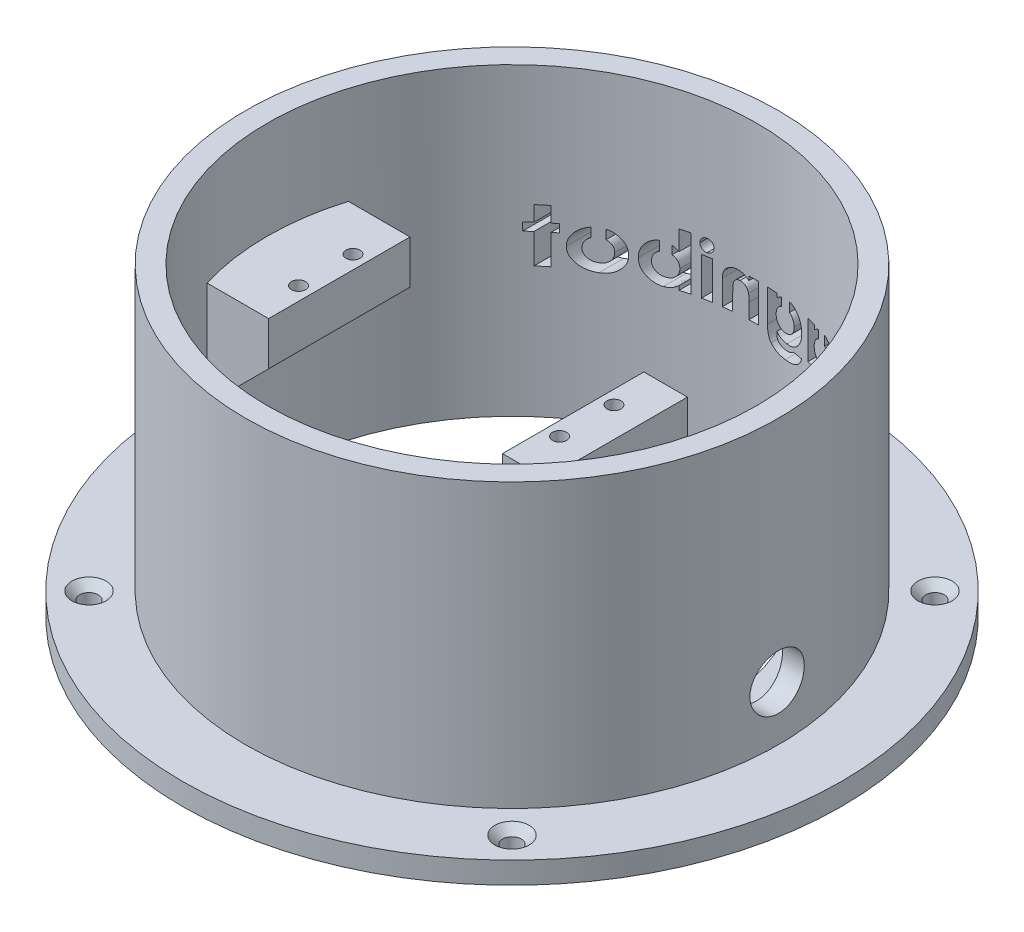
SolidWorks part; units mm, degrees
ref_plane "Front Plane" through (0, 0, 0) normal (0, 0, 1) x (1, 0, 0)
ref_plane "Top Plane" through (0, 0, 0) normal (0, 1, 0) x (1, 0, 0)
ref_plane "Right Plane" through (0, 0, 0) normal (1, 0, 0) x (0, 0, -1)
sketch "Sketch1" plane through (0, 0, 0) normal (0, 1, 0) x (1, 0, 0)
  circle A0 centre (0, 0) radius 60.625
  circle A1 centre (0, 0) radius 45
  dimension "D1" = 121.25
  dimension "D2" = 90
extrude "Boss-Extrude1" add sketch "Sketch1" along normal blind 4
sketch "Sketch2" plane through (0, 4, 0) normal (0, 1, 0) x (1, 0, 0)
  circle A0 centre (0, 0) radius 45 construction
  circle A1 centre (0, 0) radius 45
  circle A2 centre (0, 0) radius 49
  dimension "D1" = 4
extrude "Boss-Extrude2" add sketch "Sketch2" along normal blind 52
ref_plane "Plane1" through (0, 36, 0) normal (0, 1, 0) x (1, 0, 0)
sketch "Sketch4" plane through (0, 0, 0) normal (0, 0, 1) x (1, 0, 0)
  line L0 (-60.625, 0) -> (60.625, 0) construction
  line L1 (11.25, 38) -> (19.25, 38)
  line L2 (11.25, 38) -> (11.25, 0)
  line L3 (11.25, 0) -> (19.25, 0)
  line L4 (19.25, 38) -> (19.25, 0)
  line L5 (49, 56) -> (-49, 56) construction
  line L6 (-45, 56) -> (-45, 4)
  line L7 (-31.75, 38) -> (-46.75, 38)
  line L8 (-31.75, 38) -> (-31.75, 30)
  line L9 (-31.75, 30) -> (-46.75, 30)
  line L10 (-46.75, 38) -> (-46.75, 30)
  line L11 (60.625, 4) -> (-60.625, 4) construction
  line L12 (-31.75, 30) -> (-45, 16.75)
  dimension "D1" = 11.25
  dimension "D2" = 8
  dimension "D3" = 18
  dimension "D4" = 43
  dimension "D5" = 15
  dimension "D6" = 8
  dimension "D7" = 45
  dimension "D8" = 18
extrude "Boss-Extrude4" add sketch "Sketch4" along normal mid plane 26 contours L9 L8 L7 L6 | L12 L9 L6 | L1 L4 L3 L2 region at (-38.375, 34, 0) region at (-40.5833, 25.5833, 0)
sketch "Sketch5" plane through (0, 0, 0) normal (0, -1, 0) x (1, 0, 0)
  line L0 (11.25, 13) -> (29.0674, 34.3524)
  line L1 (11.25, -13) -> (29.0674, -34.3524)
  line L2 (11.25, 13) -> (11.25, -13)
  circle A0 centre (0, 0) radius 45 construction
  arc A1 (29.0674, -34.3524) -> (29.0674, 34.3524) centre (0, 0) ccw
extrude "Boss-Extrude5" add sketch "Sketch5" against normal up to surface (4 mm away) contours L0 A1 L1 L2 up to face at (0, 4, 60.625)
sketch "Sketch7" plane through (0, 38, 0) normal (0, 1, 0) x (1, 0, 0)
  line L0 (-31.75, -13) -> (-31.75, 13) construction
  circle A0 centre (-34.25, 5) radius 1.3
  circle A1 centre (-34.25, -5) radius 1.3
  circle A2 centre (13.75, 5) radius 1.3
  circle A3 centre (13.75, -5) radius 1.3
  dimension "D1" = 2.6
  dimension "D2" = 2.6
  dimension "D3" = 10
  dimension "D4" = 5
  dimension "D5" = 2.5
  dimension "D7" = 48
  dimension "D6" = 2
extrude "Cut-Extrude4" cut sketch "Sketch7" against normal blind 7.2
sketch "Sketch9" plane through (11.25, 0, 0) normal (-1, 0, 0) x (0, 0, 1)
  line L0 (13, 0) -> (-13, 0) construction
  line L1 (-5, 29) -> (5, 29)
  line L2 (-5, 29) -> (-5, 0)
  line L3 (-5, 0) -> (5, 0)
  line L4 (5, 29) -> (5, 0)
  line L5 (-5, 29) -> (5, 0) construction
  line L6 (-5, 0) -> (5, 29) construction
  line L7 (0, 0) -> (0, 29) construction
  line L8 (13, 38) -> (-13, 38) construction
  line L10 (5, 5) -> (-5, 5)
  point P0 (0, 14.5)
  dimension "D1" = 10
  dimension "D2" = 9
  dimension "D3" = 5
extrude "Cut-Extrude7" cut sketch "Sketch9" against normal up to surface (8 mm away) contours L10 L4 L1 L2 region at (11.25, 17, 0) up to face at (19.25, 21, 0)
ref_plane "Plane2" through (49, 0, 0) normal (1, 0, 0) x (0, 0, -1)
sketch "Sketch11" plane through (49, 0, 0) normal (1, 0, 0) x (0, 0, -1)
  circle A0 centre (0, 14) radius 5
  dimension "D1" = 10
  dimension "D2" = 14
extrude "Cut-Extrude8" cut sketch "Sketch11" against normal up to next
sketch "Sketch12" plane through (0, 4, 0) normal (0, 1, 0) x (1, 0, 0)
  line L5 (27.25, 19.6878) -> (27.25, -19.6878)
  line L6 (27.25, 19.6878) -> (27.25, -19.6878)
  line L9 (24.25, 16.0926) -> (24.25, -16.0926)
  line L10 (19.25, -13) -> (19.25, 13) construction
  line L18 (27.25, -19.6878) -> (29.4795, -22.3597)
  line L19 (29.4795, 22.3597) -> (27.25, 19.6878)
  line L21 (24.25, -16.0926) -> (29.4795, -22.3597)
  line L22 (29.4795, 22.3597) -> (24.25, 16.0926)
  arc A2 (29.4795, -22.3597) -> (29.4795, 22.3597) centre (0, 0) ccw
  arc A3 (29.4795, -22.3597) -> (29.4795, 22.3597) centre (0, 0) ccw
  dimension "D2" = 5
  dimension "D1" = 8
extrude "Cut-Extrude9" cut sketch "Sketch12" against normal through all contours L21 A3 L22 L6 | L6 L22 L9 L21 region at (31.3175, 4, 0) region at (25.8002, 4, 0)
sketch "Sketch14" plane through (0, 4, 0) normal (0, 1, 0) x (1, 0, 0)
  line L0 (0, 0) -> (-38.8909, 38.8909) construction
  line L1 (11.25, 13) -> (19.25, 13) construction
  circle A0 centre (-38.8909, 38.8909) radius 1.5
  circle A1 centre (38.8909, 38.8909) radius 1.5
  circle A2 centre (38.8909, -38.8909) radius 1.5
  circle A3 centre (-38.8909, -38.8909) radius 1.5
  point P15 (0, 0)
  dimension "D1" = 3
  dimension "D2" = 55
  dimension "D3" = 135
  dimension "D4" = 4
hole_wizard "CSK for M3 Countersunk Flat Head Screw1" positions "Sketch15" profile "Sketch17" countersink size "M3" standard "DIN" end condition up to next
sketch "Sketch15" plane through (0, 4, 0) normal (0, 1, 0) x (1, 0, 0)
  point P0 (-38.8909, 38.8909)
  point P3 (-38.8909, -38.8909)
  point P6 (38.8909, -38.8909)
  point P9 (38.8909, 38.8909)
sketch "Sketch17" plane through (-38.8909, 4, -38.8909) normal (1, 0, 0) x (0, 0, 1)
  line L0 (0, 0) -> (0, 4)
  line L1 (0, 4) -> (1.7, 4)
  line L2 (1.7, 4) -> (1.7, 1.45)
  line L3 (1.7, 1.45) -> (3.15, 0)
  line L5 (3.15, 0) -> (0, 0)
  line L6 (-1.7, 1.45) -> (-3.15, 0) construction
  line L11 (0, -6.35) -> (0, 107.95) construction
  dimension "Thru Hole Dia." = 3.4
  dimension "Thru Hole Depth" = 4
  dimension "Near C'Sink Dia." = 6.3
  dimension "Near C'Sink Angle" = 90
sketch "Sketch18" plane through (0, 0, -13) normal (0, 0, -1) x (-1, 0, 0)
  line L1 (28.0255, 33.7692) -> (29.7351, 33.7692)
  line L2 (29.7351, 33.7692) -> (29.7351, 30.9606)
  line L3 (29.7351, 30.9606) -> (30.8341, 30.9606)
  line L4 (30.8341, 30.9606) -> (30.8341, 29.4952)
  line L5 (30.8341, 29.4952) -> (29.7351, 29.4952)
  line L6 (29.7351, 29.4952) -> (29.7351, 24)
  line L7 (29.7351, 24) -> (28.0255, 24)
  line L8 (28.0255, 24) -> (28.0255, 29.4952)
  line L9 (28.0255, 29.4952) -> (27.1707, 29.4952)
  line L10 (27.1707, 29.4952) -> (27.1707, 30.9606)
  line L11 (27.1707, 30.9606) -> (28.0255, 30.9606)
  line L12 (28.0255, 30.9606) -> (28.0255, 33.7692)
  line L13 (12.5168, 33.7692) -> (12.5168, 30.1497)
  line L14 (12.5168, 24.7594) -> (12.5168, 24)
  line L15 (12.5168, 24) -> (10.8072, 24)
  line L16 (10.8072, 24) -> (10.8072, 33.7692)
  line L17 (10.8072, 33.7692) -> (12.5168, 33.7692)
  line L18 (7.5101, 30.9606) -> (9.2197, 30.9606)
  line L19 (9.2197, 30.9606) -> (9.2197, 24)
  line L20 (9.2197, 24) -> (7.5101, 24)
  line L21 (7.5101, 24) -> (7.5101, 30.9606)
  line L22 (-0.3053, 30.9606) -> (1.4043, 30.9606)
  line L23 (1.4043, 30.9606) -> (1.4043, 30.2241)
  line L24 (5.9226, 28.5641) -> (5.9226, 24)
  line L25 (5.9226, 24) -> (4.213, 24)
  line L26 (4.213, 24) -> (4.213, 27.0224)
  line L27 (1.4043, 26.7705) -> (1.4043, 24)
  line L28 (1.4043, 24) -> (-0.3053, 24)
  line L29 (-0.3053, 24) -> (-0.3053, 30.9606)
  line L30 (-3.8466, 30.9606) -> (-2.0149, 30.9606)
  line L31 (-2.0149, 30.9606) -> (-2.0149, 25.0227)
  line L32 (-9.2273, 23.5115) -> (-7.3269, 23.5115)
  line L33 (-3.8466, 30.1859) -> (-3.8466, 30.9606)
  line L34 (-12.3947, 30.9606) -> (-10.6851, 30.9606)
  line L35 (-10.6851, 30.9606) -> (-10.6851, 24)
  line L36 (-10.6851, 24) -> (-12.3947, 24)
  line L37 (-12.3947, 24) -> (-12.3947, 24.7594)
  line L38 (-12.3947, 30.1764) -> (-12.3947, 30.9606)
  line L39 (-30.1014, 30.9606) -> (-28.3918, 30.9606)
  line L40 (-28.3918, 30.9606) -> (-28.3918, 30.1287)
  line L41 (-19.3553, 28.0489) -> (-19.3553, 24)
  line L42 (-19.3553, 24) -> (-21.0649, 24)
  line L43 (-21.0649, 24) -> (-21.0649, 27.4956)
  line L44 (-23.8736, 27.1082) -> (-23.8736, 24)
  line L45 (-23.8736, 24) -> (-25.5832, 24)
  line L46 (-25.5832, 24) -> (-25.5832, 27.3372)
  line L47 (-28.3918, 27.0643) -> (-28.3918, 24)
  line L48 (-28.3918, 24) -> (-30.1014, 24)
  line L49 (-30.1014, 24) -> (-30.1014, 30.9606)
  line L51 (-15.1048, 31.4629) -> (-13.3948, 31.4629)
  line L52 (-15.1048, 31.4629) -> (-15.1048, 28.9712)
  line L53 (-15.1048, 28.9712) -> (-13.3948, 28.9712)
  line L54 (-13.3948, 31.4629) -> (-13.3948, 28.9712)
  line L55 (-6.4773, 31.5143) -> (-4.7673, 31.5143)
  line L56 (-6.4773, 31.5143) -> (-6.4773, 29.0876)
  line L57 (-6.4773, 29.0876) -> (-4.7673, 29.0876)
  line L58 (-4.7673, 31.5143) -> (-4.7673, 29.0876)
  line L59 (13.5081, 31.593) -> (15.2181, 31.593)
  line L60 (13.5081, 31.593) -> (13.5081, 28.9616)
  line L61 (13.5081, 28.9616) -> (15.2181, 28.9616)
  line L62 (15.2181, 31.593) -> (15.2181, 28.9616)
  line L63 (21.9818, 31.4887) -> (23.6918, 31.4887)
  line L64 (21.9818, 31.4887) -> (21.9818, 28.7761)
  line L65 (21.9818, 28.7761) -> (23.6918, 28.7761)
  line L66 (23.6918, 31.4887) -> (23.6918, 28.7761)
  spline S0 degree 3 poles (22.7936, 31.0827) (22.9536, 31.0827) (23.1931, 31.0681) (23.5072, 31.016) (23.7386, 30.9659) (23.965, 30.8957) (24.1877, 30.8115) (24.4086, 30.7149) (24.6222, 30.5998) (24.83, 30.4751) (25.0271, 30.3374) (25.2118, 30.188) (25.3874, 30.0303) (25.5458, 29.8573) (25.6972, 29.6776) (25.8334, 29.4845) (25.9594, 29.2828) (26.0716, 29.0738) (26.169, 28.8587) (26.2536, 28.6407) (26.3198, 28.417) (26.3746, 28.1906) (26.4213, 27.88) (26.4389, 27.6443) (26.438, 27.486) knots 0 0 0 0 0.084364 0.126142 0.167706 0.209066 0.250973 0.293148 0.336041 0.378761 0.420893 0.462622 0.503914 0.545188 0.586138 0.627722 0.669585 0.711432 0.752691 0.793971 0.834592 0.875577 0.91664 1 1 1 1
  spline S1 degree 3 poles (26.438, 27.486) (26.4378, 27.3266) (26.4236, 27.0883) (26.3713, 26.7763) (26.321, 26.5461) (26.2511, 26.3218) (26.1694, 26.1) (26.0691, 25.8836) (25.9582, 25.6704) (25.8314, 25.4666) (25.6953, 25.2716) (25.5446, 25.0905) (25.3874, 24.9177) (25.2164, 24.759) (25.0341, 24.6119) (24.8423, 24.4746) (24.6396, 24.3502) (24.4285, 24.2409) (24.2126, 24.1424) (23.9906, 24.0604) (23.763, 23.9934) (23.5297, 23.9417) (23.2093, 23.8941) (22.9652, 23.8771) (22.8012, 23.8779) knots 0 0 0 0 0.083839 0.125192 0.166335 0.207602 0.24867 0.290582 0.332926 0.374978 0.416741 0.457857 0.498809 0.539516 0.58042 0.62191 0.663502 0.705394 0.746864 0.788245 0.829736 0.871532 0.913825 1 1 1 1
  spline S2 degree 3 poles (22.8012, 23.8779) (22.5631, 23.8803) (22.2083, 23.9072) (21.7532, 24.019) (21.429, 24.1339) (21.1177, 24.2814) (20.822, 24.4638) (20.5389, 24.6777) (20.2733, 24.9212) (20.03, 25.1884) (19.8174, 25.4736) (19.6369, 25.7726) (19.4887, 26.0857) (19.3743, 26.4132) (19.2623, 26.874) (19.2355, 27.2332) (19.2332, 27.4746) knots 0 0 0 0 0.126884 0.188201 0.248894 0.309599 0.371125 0.433466 0.498143 0.562593 0.625474 0.687114 0.748125 0.809457 0.871431 1 1 1 1
  spline S3 degree 3 poles (19.2332, 27.4746) (19.2336, 27.7324) (19.2684, 28.1141) (19.3922, 28.6033) (19.5227, 28.9481) (19.6897, 29.2762) (19.9647, 29.6971) (20.2255, 29.9763) (20.4143, 30.1497) knots 0 0 0 0 0.256474 0.379237 0.500978 0.622367 0.744855 1 1 1 1
  spline S4 degree 3 poles (20.4143, 30.1497) (20.5802, 30.3024) (20.8481, 30.5037) (21.2311, 30.7219) (21.5244, 30.8552) (21.8286, 30.9555) (22.2495, 31.0542) (22.575, 31.0818) (22.7936, 31.0827) knots 0 0 0 0 0.258464 0.38258 0.504991 0.627227 0.749297 1 1 1 1
  spline S5 degree 3 poles (22.8318, 29.4952) (22.7019, 29.4917) (22.5077, 29.4823) (22.2621, 29.4178) (22.0874, 29.3572) (21.9227, 29.2762) (21.7633, 29.1814) (21.6176, 29.0627) (21.4785, 28.9326) (21.3522, 28.7881) (21.2446, 28.6306) (21.1485, 28.4663) (21.0755, 28.289) (21.0153, 28.1036) (20.9595, 27.8373) (20.9404, 27.6306) (20.9428, 27.4898) knots 0 0 0 0 0.126803 0.187423 0.246518 0.306285 0.365703 0.426477 0.488622 0.550895 0.612679 0.673914 0.735734 0.798735 0.86329 1 1 1 1
  spline S6 degree 3 poles (20.9428, 27.4898) (20.9422, 27.3456) (20.9565, 27.1333) (21.0136, 26.8609) (21.0729, 26.672) (21.1476, 26.4928) (21.2392, 26.3242) (21.3487, 26.1674) (21.4728, 26.0226) (21.6088, 25.891) (21.7577, 25.7782) (21.9134, 25.6801) (22.0795, 25.6014) (22.2535, 25.5406) (22.5012, 25.4797) (22.6954, 25.468) (22.826, 25.4654) knots 0 0 0 0 0.139456 0.204809 0.268587 0.330587 0.392213 0.45361 0.515092 0.576402 0.636039 0.695407 0.753981 0.813285 0.873377 1 1 1 1
  spline S7 degree 3 poles (22.826, 25.4654) (22.9571, 25.4658) (23.1512, 25.4829) (23.3999, 25.5421) (23.5754, 25.6033) (23.7416, 25.6838) (23.899, 25.7823) (24.0491, 25.8968) (24.1868, 26.0308) (24.3144, 26.1761) (24.4262, 26.3337) (24.5196, 26.5022) (24.5963, 26.6806) (24.6557, 26.8685) (24.7119, 27.1379) (24.7308, 27.3472) (24.7284, 27.4898) knots 0 0 0 0 0.126397 0.186939 0.246099 0.305348 0.364572 0.424924 0.486952 0.54955 0.611149 0.672922 0.73501 0.798049 0.862643 1 1 1 1
  spline S8 degree 3 poles (24.7284, 27.4898) (24.7289, 27.6322) (24.7144, 27.8419) (24.6579, 28.1106) (24.5978, 28.2968) (24.5236, 28.4736) (24.4319, 28.6402) (24.3219, 28.7958) (24.1971, 28.9395) (24.0592, 29.0692) (23.9128, 29.1849) (23.7547, 29.2805) (23.5879, 29.3593) (23.4118, 29.42) (23.161, 29.4811) (22.9643, 29.4923) (22.8318, 29.4952) knots 0 0 0 0 0.13784 0.202698 0.265406 0.326938 0.388125 0.449117 0.511101 0.572086 0.632197 0.691339 0.750564 0.810546 0.871335 1 1 1 1
  spline S9 degree 3 poles (12.5168, 30.1497) (12.6689, 30.2999) (12.913, 30.5045) (13.2701, 30.721) (13.5425, 30.8554) (13.8263, 30.9547) (14.2179, 31.0586) (14.5242, 31.079) (14.7283, 31.0827) knots 0 0 0 0 0.260396 0.385476 0.507708 0.62942 0.750914 1 1 1 1
  spline S10 degree 3 poles (14.7283, 31.0827) (14.9489, 31.0835) (15.2774, 31.0537) (15.6975, 30.9454) (15.9965, 30.8341) (16.2816, 30.6893) (16.5559, 30.5161) (16.8147, 30.3071) (17.0582, 30.0704) (17.2834, 29.811) (17.4794, 29.5289) (17.6425, 29.228) (17.7809, 28.9116) (17.8817, 28.5747) (17.9877, 28.0953) (18.0097, 27.72) (18.012, 27.4669) knots 0 0 0 0 0.12138 0.180256 0.238142 0.296489 0.355776 0.416247 0.479076 0.54232 0.604902 0.667516 0.730346 0.794405 0.860608 1 1 1 1
  spline S11 degree 3 poles (18.012, 27.4669) (18.0112, 27.2212) (17.9853, 26.8569) (17.8789, 26.39) (17.7693, 26.061) (17.6298, 25.7471) (17.4595, 25.4483) (17.2574, 25.1658) (17.0264, 24.9033) (16.774, 24.6656) (16.511, 24.4523) (16.2322, 24.2776) (15.9446, 24.1299) (15.6435, 24.0172) (15.2231, 23.91) (14.8966, 23.875) (14.6767, 23.8779) knots 0 0 0 0 0.135343 0.199959 0.263049 0.325881 0.388744 0.451973 0.516706 0.580831 0.6426 0.702706 0.761562 0.820266 0.879182 1 1 1 1
  spline S12 degree 3 poles (14.6767, 23.8779) (14.4813, 23.879) (14.1903, 23.9014) (13.8164, 23.9898) (13.5471, 24.0796) (13.2849, 24.2024) (12.9279, 24.4129) (12.6786, 24.6134) (12.5168, 24.7594) knots 0 0 0 0 0.245253 0.364043 0.481077 0.600625 0.726476 1 1 1 1
  spline S13 degree 3 poles (14.3581, 29.4952) (14.2224, 29.4925) (14.0206, 29.4811) (13.7637, 29.4198) (13.5821, 29.3613) (13.4104, 29.2824) (13.2472, 29.1868) (13.0939, 29.0727) (12.9496, 28.9448) (12.82, 28.8008) (12.7049, 28.647) (12.6094, 28.4813) (12.5298, 28.3059) (12.4697, 28.1188) (12.409, 27.8506) (12.3972, 27.6408) (12.3947, 27.4994) knots 0 0 0 0 0.129944 0.191681 0.251804 0.311878 0.37178 0.43216 0.494106 0.5556 0.61683 0.677256 0.737884 0.800505 0.864611 1 1 1 1
  spline S14 degree 3 poles (12.3947, 27.4994) (12.3973, 27.3547) (12.409, 27.1406) (12.4693, 26.8672) (12.5306, 26.6767) (12.6089, 26.497) (12.7043, 26.3272) (12.8207, 26.1712) (12.9489, 26.0235) (13.094, 25.8938) (13.2466, 25.7775) (13.4104, 25.6817) (13.5829, 25.6041) (13.7629, 25.5396) (14.0209, 25.4803) (14.2222, 25.4676) (14.3581, 25.4654) knots 0 0 0 0 0.137034 0.201676 0.264245 0.325918 0.386785 0.447889 0.509667 0.571399 0.631536 0.690841 0.750317 0.810229 0.871351 1 1 1 1
  spline S15 degree 3 poles (14.3581, 25.4654) (14.4904, 25.4663) (14.6858, 25.4825) (14.9372, 25.5423) (15.1143, 25.6051) (15.2837, 25.6869) (15.4466, 25.7826) (15.5976, 25.9021) (15.7426, 26.0336) (15.8723, 26.1818) (15.9886, 26.3392) (16.0864, 26.5074) (16.164, 26.6867) (16.2281, 26.8738) (16.2876, 27.1426) (16.2999, 27.3521) (16.3024, 27.4936) knots 0 0 0 0 0.1264 0.186368 0.246314 0.305548 0.365765 0.426397 0.489164 0.552425 0.614149 0.675935 0.737677 0.800494 0.864605 1 1 1 1
  spline S16 degree 3 poles (16.3024, 27.4936) (16.2994, 27.6337) (16.2886, 27.8419) (16.2268, 28.1069) (16.1694, 28.2934) (16.0892, 28.4684) (15.9943, 28.634) (15.8827, 28.7908) (15.7531, 28.9344) (15.6111, 29.0651) (15.4595, 29.1807) (15.2988, 29.2792) (15.127, 29.3568) (14.9481, 29.4206) (14.6922, 29.4804) (14.4927, 29.4929) (14.3581, 29.4952) knots 0 0 0 0 0.134802 0.198611 0.260756 0.321667 0.382903 0.4437 0.505935 0.568128 0.628667 0.688638 0.748437 0.809234 0.870665 1 1 1 1
  spline S17 degree 3 poles (8.3611, 33.8913) (8.5057, 33.8937) (8.7226, 33.8489) (8.977, 33.7027) (9.1452, 33.5539) (9.285, 33.3759) (9.4295, 33.1075) (9.4611, 32.8768) (9.4639, 32.7255) knots 0 0 0 0 0.242963 0.363855 0.490606 0.61874 0.7433 1 1 1 1
  spline S18 degree 3 poles (9.4639, 32.7255) (9.4628, 32.5754) (9.4267, 32.3489) (9.2879, 32.0806) (9.147, 31.9053) (8.9806, 31.7588) (8.732, 31.6103) (8.5162, 31.5712) (8.3744, 31.5712) knots 0 0 0 0 0.256469 0.381955 0.510704 0.637377 0.757775 1 1 1 1
  spline S19 degree 3 poles (8.3744, 31.5712) (8.2284, 31.5686) (8.0103, 31.614) (7.7524, 31.7591) (7.5849, 31.9109) (7.4436, 32.0902) (7.3049, 32.3653) (7.2655, 32.5959) (7.2659, 32.7503) knots 0 0 0 0 0.242759 0.363443 0.489711 0.617482 0.74228 1 1 1 1
  spline S20 degree 3 poles (7.2659, 32.7503) (7.2683, 32.8988) (7.3018, 33.124) (7.4428, 33.3874) (7.5816, 33.5622) (7.7483, 33.7082) (8.0025, 33.8499) (8.2174, 33.8925) (8.3611, 33.8913) knots 0 0 0 0 0.255027 0.378937 0.506523 0.634371 0.754976 1 1 1 1
  spline S21 degree 3 poles (1.4043, 30.2241) (1.5881, 30.3723) (1.8638, 30.5692) (2.2391, 30.781) (2.4966, 30.8962) (2.749, 30.9789) (3.0835, 31.0586) (3.3399, 31.0837) (3.5108, 31.0827) knots 0 0 0 0 0.304989 0.436681 0.556242 0.668759 0.779379 1 1 1 1
  spline S22 degree 3 poles (3.5108, 31.0827) (3.6804, 31.0808) (3.9334, 31.0645) (4.2568, 30.9851) (4.4874, 30.9076) (4.7072, 30.8051) (4.9922, 30.6415) (5.182, 30.4798) (5.3025, 30.3653) knots 0 0 0 0 0.257369 0.381171 0.503299 0.625248 0.747811 1 1 1 1
  spline S23 degree 3 poles (5.3025, 30.3653) (5.4059, 30.2627) (5.5432, 30.0886) (5.6853, 29.8262) (5.7737, 29.6095) (5.8389, 29.3729) (5.908, 29.0248) (5.9215, 28.7507) (5.9226, 28.5641) knots 0 0 0 0 0.22321 0.337546 0.456528 0.581244 0.713405 1 1 1 1
  spline S24 degree 3 poles (4.213, 27.0224) (4.2125, 27.2112) (4.2108, 27.4817) (4.1962, 27.8244) (4.1868, 28.0428) (4.1682, 28.2348) (4.1514, 28.4014) (4.1257, 28.5411) (4.0922, 28.6915) (4.0338, 28.8525) (3.943, 29.0221) (3.8279, 29.1662) (3.6932, 29.2858) (3.5389, 29.3803) (3.303, 29.4721) (3.1097, 29.4957) (2.9785, 29.4952) knots 0 0 0 0 0.179518 0.256937 0.32593 0.387213 0.440139 0.484952 0.522188 0.586422 0.647004 0.704202 0.760716 0.817414 0.875213 1 1 1 1
  spline S25 degree 3 poles (2.9785, 29.4952) (2.8055, 29.4934) (2.5449, 29.4553) (2.234, 29.3024) (2.0255, 29.1462) (1.8416, 28.9531) (1.6327, 28.637) (1.531, 28.3636) (1.4845, 28.171) knots 0 0 0 0 0.240658 0.35739 0.477137 0.600009 0.725225 1 1 1 1
  spline S26 degree 3 poles (1.4845, 28.171) (1.4665, 28.1021) (1.4533, 27.9851) (1.4322, 27.8146) (1.4255, 27.6513) (1.4141, 27.4645) (1.4081, 27.168) (1.4044, 26.934) (1.4043, 26.7705) knots 0 0 0 0 0.151476 0.251213 0.366854 0.500124 0.650932 1 1 1 1
  spline S27 degree 3 poles (-2.0149, 25.0227) (-2.0161, 24.7489) (-2.0329, 24.3502) (-2.1079, 23.8416) (-2.1856, 23.5018) (-2.2863, 23.192) (-2.4455, 22.8255) (-2.6034, 22.5793) (-2.7266, 22.4354) knots 0 0 0 0 0.300234 0.436257 0.562885 0.681681 0.792784 1 1 1 1
  spline S28 degree 3 poles (-2.7266, 22.4354) (-2.8834, 22.2492) (-3.1574, 22.0013) (-3.5792, 21.7441) (-3.9268, 21.5849) (-4.3051, 21.4638) (-4.8649, 21.3434) (-5.3059, 21.3128) (-5.6078, 21.3135) knots 0 0 0 0 0.228421 0.343997 0.462956 0.586703 0.716303 1 1 1 1
  spline S29 degree 3 poles (-5.6078, 21.3135) (-5.9233, 21.3133) (-6.3802, 21.3376) (-6.9551, 21.4475) (-7.33, 21.5582) (-7.6699, 21.7012) (-7.9812, 21.8726) (-8.2633, 22.0776) (-8.5206, 22.3079) (-8.7467, 22.5689) (-9.0083, 22.9588) (-9.1528, 23.2846) (-9.2273, 23.5115) knots 0 0 0 0 0.207411 0.299345 0.383942 0.46371 0.541137 0.616855 0.692287 0.767513 0.843065 1 1 1 1
  spline S30 degree 3 poles (-7.3269, 23.5115) (-7.2424, 23.411) (-7.0944, 23.2762) (-6.8653, 23.1368) (-6.6744, 23.0501) (-6.4646, 22.9844) (-6.1522, 22.9154) (-5.9045, 22.902) (-5.7356, 22.901) knots 0 0 0 0 0.223655 0.337943 0.455777 0.579824 0.711809 1 1 1 1
  spline S31 degree 3 poles (-5.7356, 22.901) (-5.5252, 22.8993) (-5.2245, 22.9236) (-4.8512, 23.0143) (-4.621, 23.1109) (-4.4224, 23.227) (-4.2567, 23.3619) (-4.1198, 23.5105) (-4.0303, 23.6502) (-3.9771, 23.777) (-3.9409, 23.8865) (-3.9134, 24.0127) (-3.8884, 24.1533) (-3.8697, 24.31) (-3.8523, 24.5498) (-3.8442, 24.7376) (-3.8466, 24.8682) knots 0 0 0 0 0.197721 0.282266 0.359994 0.431569 0.49787 0.56009 0.620807 0.652682 0.689174 0.72906 0.773983 0.823375 0.87735 1 1 1 1
  spline S32 degree 3 poles (-3.8466, 24.8682) (-3.9891, 24.7215) (-4.2155, 24.5237) (-4.5479, 24.3175) (-4.7977, 24.1973) (-5.0596, 24.1094) (-5.435, 24.0229) (-5.7297, 24.001) (-5.9302, 24) knots 0 0 0 0 0.263928 0.385524 0.503705 0.620733 0.741155 1 1 1 1
  spline S33 degree 3 poles (-5.9302, 24) (-6.1529, 23.9985) (-6.4834, 24.0299) (-6.9074, 24.1357) (-7.2089, 24.2439) (-7.4948, 24.3877) (-7.7693, 24.5588) (-8.0273, 24.7661) (-8.2723, 24.9982) (-8.4938, 25.2561) (-8.6886, 25.5331) (-8.8529, 25.8273) (-8.9865, 26.1384) (-9.0929, 26.4651) (-9.1927, 26.932) (-9.2188, 27.2956) (-9.2197, 27.5413) knots 0 0 0 0 0.1237 0.183445 0.242476 0.301273 0.360988 0.421869 0.484864 0.548268 0.610431 0.67277 0.73514 0.798288 0.86338 1 1 1 1
  spline S34 degree 3 poles (-9.2197, 27.5413) (-9.2211, 27.8026) (-9.1909, 28.1873) (-9.0852, 28.6807) (-8.9753, 29.0233) (-8.8304, 29.3443) (-8.5973, 29.747) (-8.3769, 30.0193) (-8.2104, 30.1821) knots 0 0 0 0 0.269734 0.396745 0.520319 0.640547 0.759724 1 1 1 1
  spline S35 degree 3 poles (-8.2104, 30.1821) (-8.0629, 30.3284) (-7.8246, 30.5246) (-7.4774, 30.7358) (-7.2084, 30.8619) (-6.9288, 30.9621) (-6.5361, 31.0571) (-6.2309, 31.0833) (-6.0256, 31.0827) knots 0 0 0 0 0.256681 0.379784 0.501471 0.623319 0.746312 1 1 1 1
  spline S36 degree 3 poles (-6.0256, 31.0827) (-5.8329, 31.0809) (-5.544, 31.0597) (-5.1722, 30.9687) (-4.9013, 30.8759) (-4.6336, 30.7555) (-4.2695, 30.5388) (-4.0124, 30.3368) (-3.8466, 30.1859) knots 0 0 0 0 0.2398 0.357658 0.474596 0.595177 0.721609 1 1 1 1
  spline S37 degree 3 poles (-5.6173, 29.4952) (-5.7486, 29.4924) (-5.9441, 29.481) (-6.1927, 29.4198) (-6.3686, 29.3613) (-6.5347, 29.2825) (-6.6914, 29.1864) (-6.8405, 29.0749) (-6.9773, 28.9458) (-7.1041, 28.8063) (-7.2105, 28.6527) (-7.3054, 28.4939) (-7.3792, 28.3235) (-7.4401, 28.1459) (-7.4912, 27.8909) (-7.5138, 27.6945) (-7.5101, 27.5604) knots 0 0 0 0 0.130325 0.192491 0.253031 0.313597 0.374077 0.434784 0.49761 0.560052 0.621032 0.682272 0.742887 0.804621 0.867736 1 1 1 1
  spline S38 degree 3 poles (-7.5101, 27.5604) (-7.5126, 27.4216) (-7.4934, 27.218) (-7.4376, 26.9553) (-7.3761, 26.7729) (-7.2989, 26.5991) (-7.2063, 26.4341) (-7.0919, 26.2817) (-6.9648, 26.1386) (-6.8243, 26.0093) (-6.6731, 25.8968) (-6.5142, 25.7996) (-6.3442, 25.7239) (-6.1669, 25.6625) (-5.9146, 25.6021) (-5.7175, 25.5901) (-5.5849, 25.5875) knots 0 0 0 0 0.134675 0.197932 0.260448 0.321294 0.382443 0.443854 0.505984 0.568072 0.628986 0.688849 0.748568 0.809329 0.870916 1 1 1 1
  spline S39 degree 3 poles (-5.5849, 25.5875) (-5.4549, 25.585) (-5.2638, 25.604) (-5.0182, 25.6605) (-4.8459, 25.7195) (-4.6833, 25.7967) (-4.5283, 25.8887) (-4.3842, 26) (-4.2481, 26.1259) (-4.1254, 26.2659) (-4.017, 26.4176) (-3.928, 26.581) (-3.8521, 26.7535) (-3.796, 26.9376) (-3.7378, 27.2011) (-3.7243, 27.4074) (-3.7245, 27.5471) knots 0 0 0 0 0.128347 0.189068 0.248938 0.308024 0.366703 0.426834 0.487805 0.549753 0.610659 0.671749 0.733442 0.796702 0.861717 1 1 1 1
  spline S40 degree 3 poles (-3.7245, 27.5471) (-3.724, 27.6849) (-3.7381, 27.8886) (-3.7959, 28.149) (-3.8527, 28.3315) (-3.9269, 28.5039) (-4.02, 28.6647) (-4.1263, 28.8169) (-4.2516, 28.9552) (-4.3866, 29.0832) (-4.5355, 29.1914) (-4.6907, 29.2871) (-4.8576, 29.3629) (-5.034, 29.4225) (-5.2869, 29.4785) (-5.4835, 29.4978) (-5.6173, 29.4952) knots 0 0 0 0 0.135592 0.199609 0.261895 0.32322 0.383708 0.44425 0.505361 0.566852 0.626748 0.685936 0.745803 0.8065 0.868686 1 1 1 1
  spline S41 degree 3 poles (-12.3947, 24.7594) (-12.5564, 24.6133) (-12.8058, 24.4129) (-13.1627, 24.2024) (-13.4245, 24.08) (-13.6923, 23.9898) (-14.0649, 23.9011) (-14.3554, 23.8792) (-14.5508, 23.8779) knots 0 0 0 0 0.273944 0.399987 0.519719 0.636176 0.754371 1 1 1 1
  spline S42 degree 3 poles (-14.5508, 23.8779) (-14.7712, 23.8755) (-15.0979, 23.9093) (-15.5182, 24.0175) (-15.819, 24.1304) (-16.1079, 24.2769) (-16.3871, 24.453) (-16.6518, 24.6649) (-16.9042, 24.9034) (-17.1353, 25.1657) (-17.3374, 25.4483) (-17.5076, 25.7471) (-17.6472, 26.061) (-17.7568, 26.39) (-17.8632, 26.8569) (-17.8891, 27.2212) (-17.8899, 27.4669) knots 0 0 0 0 0.121092 0.179634 0.238304 0.297437 0.357507 0.419513 0.4836 0.548295 0.611487 0.674313 0.737107 0.80016 0.864737 1 1 1 1
  spline S43 degree 3 poles (-17.8899, 27.4669) (-17.8879, 27.7201) (-17.865, 28.0952) (-17.7604, 28.5752) (-17.6558, 28.9108) (-17.5211, 29.2285) (-17.357, 29.5288) (-17.1614, 29.811) (-16.936, 30.0703) (-16.6926, 30.3079) (-16.4322, 30.5148) (-16.1589, 30.6905) (-15.8723, 30.834) (-15.5726, 30.9447) (-15.1523, 31.0546) (-14.8235, 31.0829) (-14.6023, 31.0827) knots 0 0 0 0 0.139309 0.205474 0.269598 0.332253 0.39483 0.457376 0.520582 0.583374 0.644082 0.70304 0.761664 0.819844 0.878346 1 1 1 1
  spline S44 degree 3 poles (-14.6023, 31.0827) (-14.3968, 31.0851) (-14.092, 31.0547) (-13.6981, 30.9597) (-13.4159, 30.86) (-13.1421, 30.7337) (-12.7892, 30.5205) (-12.5451, 30.3239) (-12.3947, 30.1764) knots 0 0 0 0 0.251537 0.373434 0.495667 0.61768 0.742091 1 1 1 1
  spline S45 degree 3 poles (-14.2436, 29.4952) (-14.377, 29.4931) (-14.5751, 29.4799) (-14.8293, 29.4209) (-15.0069, 29.3568) (-15.1771, 29.2787) (-15.3374, 29.1808) (-15.489, 29.0651) (-15.631, 28.9344) (-15.7605, 28.7908) (-15.8722, 28.634) (-15.9671, 28.4684) (-16.0473, 28.2934) (-16.1047, 28.1069) (-16.1665, 27.8419) (-16.1773, 27.6337) (-16.1803, 27.4936) knots 0 0 0 0 0.128421 0.189996 0.250359 0.309744 0.369856 0.430537 0.492876 0.555257 0.616197 0.677577 0.738631 0.800922 0.864882 1 1 1 1
  spline S46 degree 3 poles (-16.1803, 27.4936) (-16.1778, 27.3521) (-16.1656, 27.1426) (-16.106, 26.8738) (-16.042, 26.6866) (-15.9639, 26.5079) (-15.8688, 26.3387) (-15.752, 26.1818) (-15.6223, 26.0337) (-15.4774, 25.9014) (-15.3249, 25.7839) (-15.1629, 25.6856) (-14.993, 25.6061) (-14.8159, 25.5415) (-14.5641, 25.4833) (-14.3684, 25.466) (-14.236, 25.4654) knots 0 0 0 0 0.135365 0.199461 0.262264 0.323991 0.385461 0.447171 0.510418 0.573171 0.634271 0.693954 0.753723 0.813084 0.873629 1 1 1 1
  spline S47 degree 3 poles (-14.236, 25.4654) (-14.1001, 25.4676) (-13.8988, 25.4803) (-13.6408, 25.5396) (-13.4608, 25.6041) (-13.2882, 25.6817) (-13.1246, 25.7776) (-12.9718, 25.8931) (-12.8289, 26.0249) (-12.698, 26.1697) (-12.5848, 26.3286) (-12.4862, 26.4963) (-12.4087, 26.6768) (-12.3471, 26.8671) (-12.2869, 27.1406) (-12.2752, 27.3547) (-12.2726, 27.4994) knots 0 0 0 0 0.128662 0.18979 0.249707 0.309189 0.3685 0.428644 0.489937 0.552121 0.612878 0.67405 0.735729 0.798305 0.862953 1 1 1 1
  spline S48 degree 3 poles (-12.2726, 27.4994) (-12.2751, 27.6409) (-12.2869, 27.8506) (-12.3476, 28.1188) (-12.4078, 28.3058) (-12.4868, 28.482) (-12.5854, 28.6457) (-12.6974, 28.8023) (-12.8297, 28.9432) (-12.9718, 29.0741) (-13.1269, 29.1861) (-13.2901, 29.2825) (-13.4624, 29.3617) (-13.6455, 29.4197) (-13.9043, 29.4809) (-14.1072, 29.4927) (-14.2436, 29.4952) knots 0 0 0 0 0.135096 0.199063 0.261548 0.322044 0.382646 0.443385 0.505155 0.566516 0.627254 0.687026 0.74697 0.807539 0.869733 1 1 1 1
  spline S49 degree 3 poles (-28.3918, 30.1287) (-28.2465, 30.2839) (-28.0093, 30.4927) (-27.6591, 30.7169) (-27.3865, 30.8514) (-27.1007, 30.954) (-26.6986, 31.0562) (-26.3842, 31.0813) (-26.1728, 31.0827) knots 0 0 0 0 0.256336 0.379114 0.500551 0.622116 0.744715 1 1 1 1
  spline S50 degree 3 poles (-26.1728, 31.0827) (-25.9608, 31.0835) (-25.6457, 31.0468) (-25.2501, 30.9122) (-24.9764, 30.771) (-24.7204, 30.5963) (-24.4112, 30.3022) (-24.2256, 30.0355) (-24.1235, 29.8425) knots 0 0 0 0 0.251955 0.373414 0.494801 0.617069 0.74062 1 1 1 1
  spline S51 degree 3 poles (-24.1235, 29.8425) (-23.9889, 30.0382) (-23.7549, 30.3055) (-23.3883, 30.5963) (-23.0919, 30.7723) (-22.7775, 30.9117) (-22.333, 31.046) (-21.9839, 31.0836) (-21.7499, 31.0827) knots 0 0 0 0 0.255445 0.379177 0.501905 0.625344 0.748278 1 1 1 1
  spline S52 degree 3 poles (-21.7499, 31.0827) (-21.5115, 31.0848) (-21.1601, 31.0429) (-20.7197, 30.8991) (-20.4251, 30.7465) (-20.1587, 30.5654) (-19.9317, 30.3515) (-19.7433, 30.1122) (-19.6207, 29.8888) (-19.5414, 29.6912) (-19.4935, 29.5193) (-19.4487, 29.3274) (-19.4165, 29.1128) (-19.3865, 28.8776) (-19.3622, 28.5206) (-19.355, 28.2417) (-19.3553, 28.0489) knots 0 0 0 0 0.160904 0.236986 0.311729 0.384307 0.453908 0.521546 0.589232 0.625293 0.665128 0.709632 0.758368 0.811604 0.869763 1 1 1 1
  spline S53 degree 3 poles (-21.0649, 27.4956) (-21.0681, 27.6748) (-21.0704, 27.9329) (-21.1067, 28.2594) (-21.1371, 28.4701) (-21.1807, 28.6571) (-21.2339, 28.8208) (-21.2955, 28.9614) (-21.37, 29.0788) (-21.4534, 29.1777) (-21.5461, 29.2625) (-21.6473, 29.3348) (-21.7578, 29.3965) (-21.8805, 29.4381) (-22.0594, 29.4832) (-22.2008, 29.4974) (-22.2975, 29.4952) knots 0 0 0 0 0.200235 0.287287 0.36626 0.437683 0.50118 0.558021 0.608412 0.655743 0.701944 0.748215 0.794252 0.842505 0.892237 1 1 1 1
  spline S54 degree 3 poles (-22.2975, 29.4952) (-22.4475, 29.4962) (-22.6719, 29.4663) (-22.9494, 29.3564) (-23.1418, 29.2461) (-23.3164, 29.1082) (-23.469, 28.9446) (-23.5951, 28.7544) (-23.6824, 28.5779) (-23.737, 28.4184) (-23.7754, 28.2817) (-23.8054, 28.1272) (-23.8289, 27.9564) (-23.8514, 27.7682) (-23.867, 27.4836) (-23.8766, 27.2617) (-23.8736, 27.1082) knots 0 0 0 0 0.138577 0.206073 0.274463 0.3426 0.41074 0.480118 0.5526 0.591784 0.635663 0.683569 0.736965 0.794871 0.858421 1 1 1 1
  spline S55 degree 3 poles (-25.5832, 27.3372) (-25.5819, 27.4804) (-25.5875, 27.6872) (-25.6029, 27.9524) (-25.6183, 28.128) (-25.6361, 28.288) (-25.6617, 28.4317) (-25.6886, 28.5597) (-25.7348, 28.7052) (-25.7999, 28.8663) (-25.8972, 29.0372) (-26.0148, 29.1803) (-26.1497, 29.2968) (-26.3022, 29.3854) (-26.5292, 29.4757) (-26.7172, 29.4923) (-26.8425, 29.4952) knots 0 0 0 0 0.151067 0.218305 0.280287 0.337064 0.388152 0.434234 0.474994 0.549031 0.617296 0.681663 0.743542 0.80432 0.867013 1 1 1 1
  spline S56 degree 3 poles (-26.8425, 29.4952) (-26.9882, 29.498) (-27.205, 29.4623) (-27.476, 29.3549) (-27.6649, 29.2416) (-27.8368, 29.1004) (-27.9879, 28.9321) (-28.1134, 28.737) (-28.201, 28.5557) (-28.2548, 28.3921) (-28.2943, 28.2519) (-28.3232, 28.094) (-28.3473, 27.9201) (-28.3696, 27.73) (-28.3853, 27.4429) (-28.3948, 27.2191) (-28.3918, 27.0643) knots 0 0 0 0 0.133552 0.199705 0.26712 0.335278 0.403628 0.474205 0.547994 0.588136 0.632412 0.681857 0.735629 0.793897 0.857789 1 1 1 1
  dimension "D1" = 1.71
  dimension "D2" = 1.71
  dimension "D3" = 0.86
  dimension "D4" = 1.71
  dimension "D5" = 0.85
  dimension "D6" = 1.71
  dimension "D7" = 0.85
extrude "Cut-Extrude10" cut sketch "Sketch18" along normal blind 45 contours S56 S55 L46 L45 L44 S54 S53 L43 L42 L41 S52 S51 S50 S49 L40 L39 L49 L48 L47 | S48 S47 S46 S45 L52 S43 S42 S41 L37 L36 L35 L34 L38 S44 L54 | S40 S39 S38 S37 L56 S35 S34 S33 S32 S31 S30 L32 S29 S28 S27 L31 L30 L33 S36 L58 | S26 S25 S24 L26 L25 L24 S23 S22 S21 L23 L22 L29 L28 L27 | L21 L20 L19 L18 | S20 S19 S18 S17 | S16 S15 S14 S13 L60 S9 L13 L17 L16 L15 L14 S12 S11 S10 L62 | S8 S7 S6 S5 L64 S4 S3 S2 S1 S0 L66 | L12 L11 L10 L9 L8 L7 L6 L5 L4 L3 L2 L1 region at (-28.9138, 29.0812, -13) region at (-12.3945, 31.9594, -13) region at (-8.3649, 27.4803, -13) region at (-0.5495, 30.8663, -13) region at (2.9308, 30.8394, -13) region at (11.5399, 30.8589, -13) region at (24.8258, 27.9143, -13) region at (-21.8805, 30.1472, -13) region at (-8.3647, 32.7321, -13)
